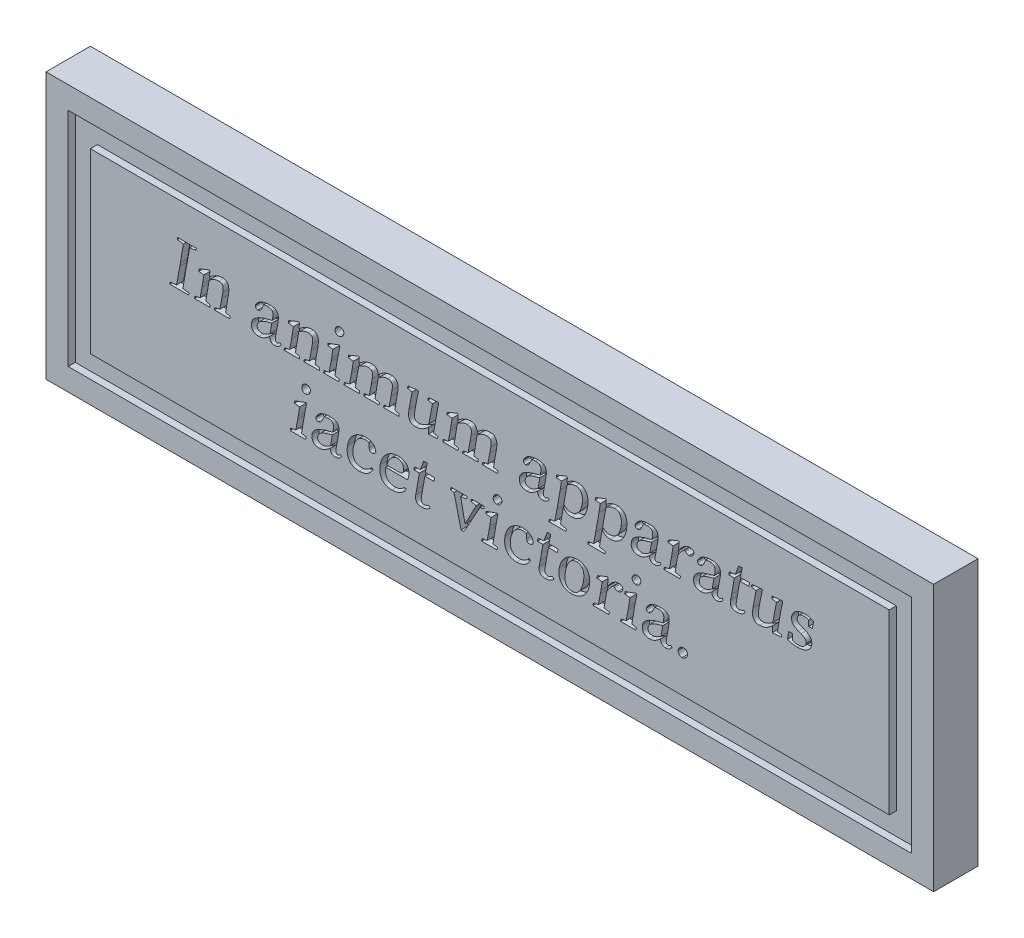
SolidWorks part; units mm, degrees
material "Acrylic (Medium-high impact)"
ref_plane "Front Plane" through (0, 0, 0) normal (0, 0, 1) x (1, 0, 0)
ref_plane "Top Plane" through (0, 0, 0) normal (0, 1, 0) x (1, 0, 0)
ref_plane "Right Plane" through (0, 0, 0) normal (1, 0, 0) x (0, 0, -1)
sketch "Sketch1" plane through (0, 0, 0) normal (0, 0, 1) x (1, 0, 0)
  line L1 (-31.75, -9.525) -> (31.75, -9.525)
  line L2 (-31.75, -9.525) -> (-31.75, 9.525)
  line L3 (-31.75, 9.525) -> (31.75, 9.525)
  line L4 (31.75, -9.525) -> (31.75, 9.525)
  line L5 (-31.75, -9.525) -> (31.75, 9.525) construction
  line L6 (-31.75, 9.525) -> (31.75, -9.525) construction
  point P0 (0, 0)
  dimension "D1" = 19.05
  dimension "D2" = 63.5
extrude "Boss-Extrude1" add sketch "Sketch1" along normal blind 3.175
sketch "Sketch2" plane through (0, 0, 3.175) normal (0, 0, 1) x (1, 0, 0)
  line L0 (-31.75, 0.7937) -> (31.75, 0.7937) construction
  line L1 (31.75, -9.525) -> (31.75, 9.525) construction
  line L2 (-31.75, 9.525) -> (-31.75, -9.525) construction
  line L3 (-26.9875, 0.7937) -> (-26.9875, 3.9687) construction
  line L4 (-26.9875, 3.9687) -> (26.9875, 3.9687) construction
  line L5 (26.9875, 3.9687) -> (26.9875, 0.7938) construction
  line L6 (-26.9875, 0.7937) -> (-26.9875, -0.7937) construction
  line L7 (-26.9875, -3.9687) -> (26.9875, -3.9687) construction
  line L8 (26.9875, -0.7937) -> (26.9875, 0.7938) construction
  line L9 (26.9875, -0.7937) -> (-26.9875, -0.7937) construction
  line L10 (-26.9875, -3.9687) -> (-26.9875, -0.7937) construction
  line L11 (26.9875, -0.7937) -> (26.9875, -3.9687) construction
  line L12 (0, -0.7937) -> (0, 0.7937) construction
  line L21 (30.1625, -7.9375) -> (30.1625, 7.9375)
  line L22 (30.1625, 7.9375) -> (-30.1625, 7.9375)
  line L23 (-30.1625, 7.9375) -> (-30.1625, -7.9375)
  line L24 (-30.1625, -7.9375) -> (30.1625, -7.9375)
  line L25 (30.1625, -7.9375) -> (30.1625, 7.9375) construction
  line L26 (30.1625, 7.9375) -> (-30.1625, 7.9375) construction
  line L27 (-30.1625, 7.9375) -> (-30.1625, -7.9375) construction
  line L28 (-30.1625, -7.9375) -> (30.1625, -7.9375) construction
  line L29 (28.575, -6.35) -> (28.575, 6.35)
  line L30 (28.575, 6.35) -> (-28.575, 6.35)
  line L31 (-28.575, 6.35) -> (-28.575, -6.35)
  line L32 (-28.575, -6.35) -> (28.575, -6.35)
  line L33 (28.575, -6.35) -> (28.575, 6.35) construction
  line L34 (28.575, 6.35) -> (-28.575, 6.35) construction
  line L35 (-28.575, 6.35) -> (-28.575, -6.35) construction
  line L36 (-28.575, -6.35) -> (28.575, -6.35) construction
  text T0 "<i>In animum apparatus</i>" font "Source Serif Pro" height 3.175
  text T1 "<i>iacet victoria.</i>" font "Source Serif Pro" height 3.175
  point P5 (0, 3.9687)
  point P18 (0, 0)
  dimension "D1" = 3.175
  dimension "D2" = 1.5875
  dimension "D3" = 53.975
  dimension "D4" = 1.5875
  dimension "D5" = 3.175
extrude "Cut-Extrude1" cut sketch "Sketch2" against normal blind 0.508
sketch "Sketch3" plane through (0, 0, 3.175) normal (0, 0, 1) x (1, 0, 0)
  line L0 (28.575, -6.35) -> (28.575, 6.35) construction
  line L1 (-28.575, -6.35) -> (28.575, -6.35) construction
  line L2 (-28.575, 6.35) -> (-28.575, -6.35) construction
  line L3 (28.575, 6.35) -> (-28.575, 6.35) construction
  line L4 (30.1625, -7.9375) -> (30.1625, 7.9375) construction
  line L5 (-30.1625, -7.9375) -> (30.1625, -7.9375) construction
  line L6 (-30.1625, 7.9375) -> (-30.1625, -7.9375) construction
  line L7 (30.1625, 7.9375) -> (-30.1625, 7.9375) construction
  line L8 (28.575, -6.35) -> (28.575, 6.35)
  line L9 (-28.575, -6.35) -> (28.575, -6.35)
  line L10 (-28.575, 6.35) -> (-28.575, -6.35)
  line L11 (28.575, 6.35) -> (-28.575, 6.35)
  line L12 (30.1625, -7.9375) -> (30.1625, 7.9375)
  line L13 (-30.1625, -7.9375) -> (30.1625, -7.9375)
  line L14 (-30.1625, 7.9375) -> (-30.1625, -7.9375)
  line L15 (30.1625, 7.9375) -> (-30.1625, 7.9375)
extrude "Cut-Extrude2" cut sketch "Sketch3" against normal blind 0.508 contours L12 L15 L14 L13 L11 L8 L9 L10
